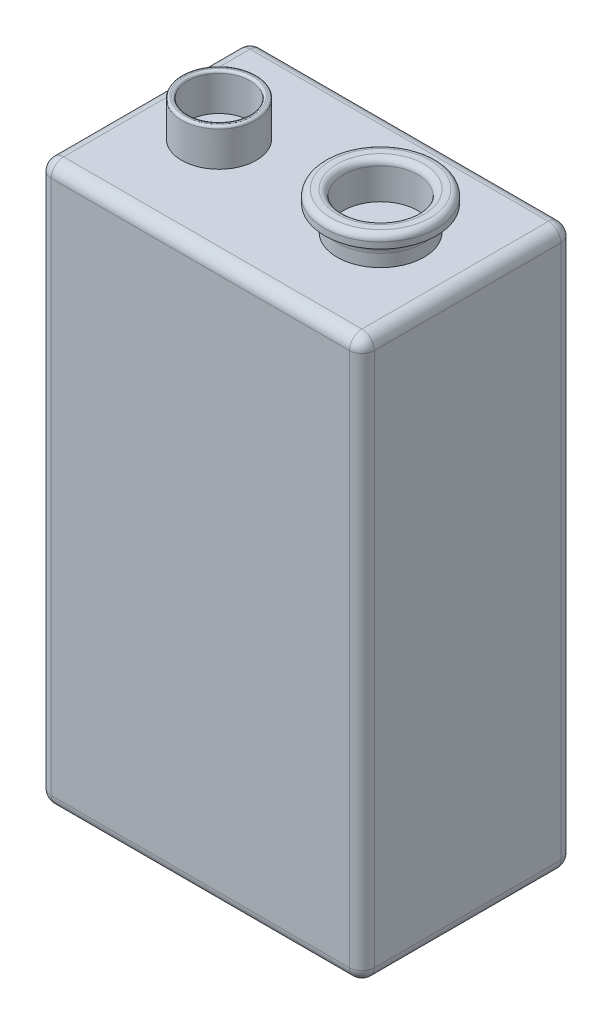
SolidWorks part; units mm, degrees
ref_plane "Front Plane" through (0, 0, 0) normal (0, 0, 1) x (1, 0, 0)
ref_plane "Top Plane" through (0, 0, 0) normal (0, 1, 0) x (1, 0, 0)
ref_plane "Right Plane" through (0, 0, 0) normal (1, 0, 0) x (0, 0, -1)
sketch "Sketch1" plane through (0, 0, 0) normal (0, 1, 0) x (1, 0, 0)
  line L1 (13, 8.5) -> (-13, 8.5)
  line L2 (13, 8.5) -> (13, -8.5)
  line L3 (13, -8.5) -> (-13, -8.5)
  line L4 (-13, 8.5) -> (-13, -8.5)
  line L5 (13, 8.5) -> (-13, -8.5) construction
  line L6 (13, -8.5) -> (-13, 8.5) construction
  point P0 (0, 0)
  dimension "D1" = 26
  dimension "D2" = 17
extrude "Boss-Extrude1" add sketch "Sketch1" along normal blind 45
fillet "Fillet1" radius 1 12 edges at (0, 0, 8.5) (13, 0, 0) (0, 0, -8.5) (-13, 0, 0) (0, 45, -8.5) (13, 45, 0) (0, 45, 8.5) (-13, 45, 0) (-13, 22.5, -8.5) (13, 22.5, -8.5) (-13, 22.5, 8.5) (13, 22.5, 8.5)
sketch "Sketch2" plane through (0, 45, 0) normal (0, 1, 0) x (1, 0, 0)
  line L0 (-13, -7.5) -> (-13, 7.5) construction
  circle A0 centre (-7, 0) radius 3
  circle A1 centre (-7, 0) radius 2.5
  point P3 (-13, 0)
  dimension "D1" = 6
  dimension "D2" = 5
  dimension "D3" = 6
extrude "Boss-Extrude2" add sketch "Sketch2" along normal blind 3
sketch "Sketch3" plane through (0, 45, 0) normal (0, 1, 0) x (1, 0, 0)
  line L0 (12, -7.5) -> (12, 7.5) construction
  circle A0 centre (6, 0) radius 3.5
  circle A1 centre (6, 0) radius 3
  point P3 (12, 0)
  dimension "D1" = 7
  dimension "D2" = 6
  dimension "D3" = 6
extrude "Boss-Extrude3" add sketch "Sketch3" along normal blind 2
sketch "Sketch4" plane through (0, 47, 0) normal (0, 1, 0) x (1, 0, 0)
  circle A0 centre (6, 0) radius 3
  circle A1 centre (6, 0) radius 4.5
  dimension "D1" = 9
extrude "Boss-Extrude4" add sketch "Sketch4" along normal blind 1
fillet "Fillet4" radius 1 1 edges at (6, 47, 3.5)
fillet "Fillet5" radius 0.5 2 edges at (6, 48, 3) (6, 48, 4.5)
fillet "Fillet6" radius 0.2 2 edges at (-7, 48, 2.5) (-7, 48, 3)
ref_plane "Plane1" through (0, 24, 0) normal (0, 1, 0) x (1, 0, 0)
